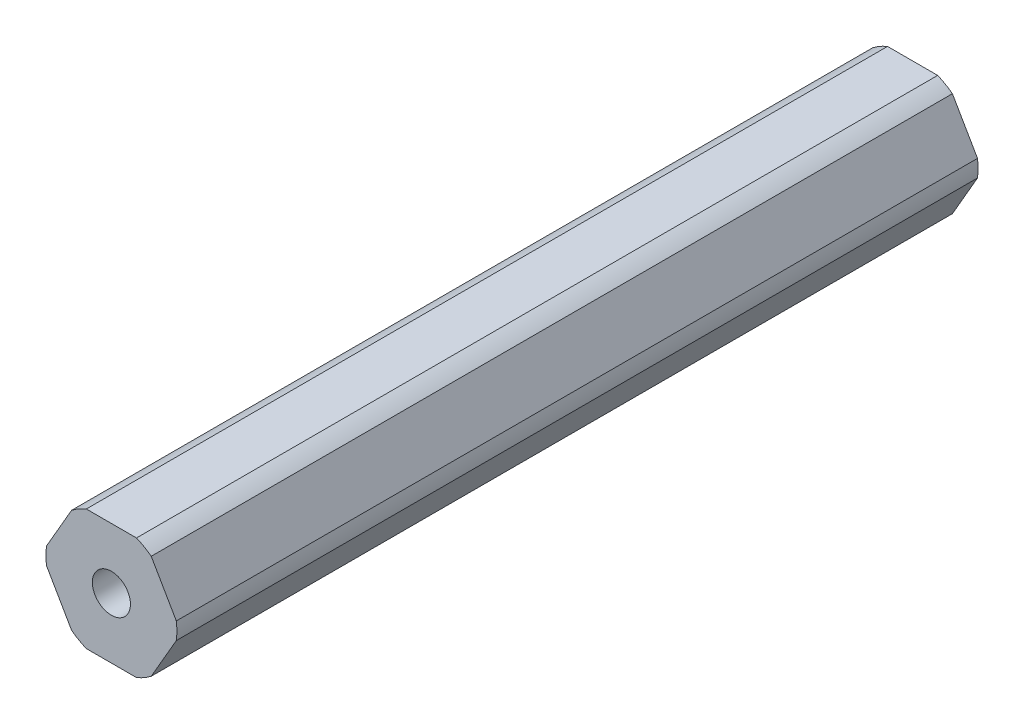
SolidWorks part; units mm, degrees
material "6061-T6 (SS)"
ref_plane "Front Plane" through (0, 0, 0) normal (0, 0, 1) x (1, 0, 0)
ref_plane "Top Plane" through (0, 0, 0) normal (0, 1, 0) x (1, 0, 0)
ref_plane "Right Plane" through (0, 0, 0) normal (1, 0, 0) x (0, 0, -1)
sketch "Sketch1" plane through (0, 0, 0) normal (0, 0, 1) x (1, 0, 0)
  line L1 (3.6662, 6.35) -> (-3.6662, 6.35)
  line L2 (-3.6662, 6.35) -> (-7.3323, 0)
  line L3 (-7.3323, 0) -> (-3.6662, -6.35)
  line L4 (-3.6662, -6.35) -> (3.6662, -6.35)
  line L5 (3.6662, -6.35) -> (7.3323, 0)
  line L6 (7.3323, 0) -> (3.6662, 6.35)
  circle A0 centre (0, 0) radius 6.35 construction
  circle A1 centre (0, 0) radius 2
  circle A2 centre (0, 0) radius 6.875
  point P1 (0, 6.35)
  dimension "D2" = 13.75
  dimension "D3" = 4
  dimension "D1" = 12.7
extrude "Boss-Extrude1" add sketch "Sketch1" along normal mid plane 84.1375 contours L6 A2 L1 L2 L3 L4 L5 A1 region at (3.3439, 5.7918, 0)
sketch "Sketch4" plane through (0, 0, 42.0688) normal (0, 0, 1) x (1, 0, 0)
  circle A0 centre (0, 0) radius 6.35
  circle A2 centre (0, 0) radius 2.4892
  dimension "D1" = 12.7
  dimension "D2" = 4.9784
equation "\"D2@Sketch1\"=13.75mm"
equation "\"D3@Sketch1\"=4mm"
